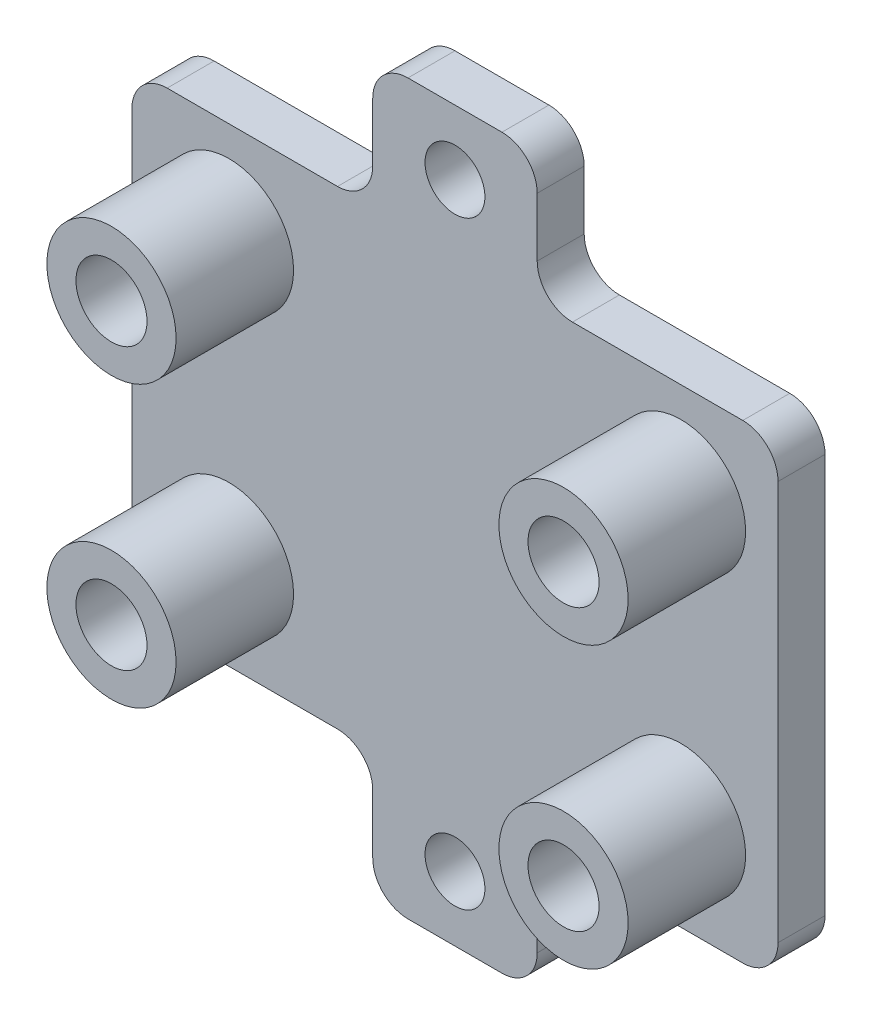
SolidWorks part; units mm, degrees
material "ABS"
ref_plane "X-Y Datum" through (0, 0, 0) normal (0, 0, 1) x (1, 0, 0)
ref_plane "X-Z Datum" through (0, 0, 0) normal (0, 1, 0) x (1, 0, 0)
ref_plane "Y-Z Datum" through (0, 0, 0) normal (1, 0, 0) x (0, 0, -1)
sketch "Sketch1" plane through (0, 0, 0) normal (0, 0, 1) x (1, 0, 0)
  line L1 (-22.987, 15.621) -> (22.987, 15.621) construction
  line L2 (-22.987, 15.621) -> (-22.987, -15.621) construction
  line L3 (-22.987, -15.621) -> (22.987, -15.621) construction
  line L4 (22.987, 15.621) -> (22.987, -15.621) construction
  line L5 (-22.987, 15.621) -> (22.987, -15.621) construction
  line L6 (-22.987, -15.621) -> (22.987, 15.621) construction
  line L7 (27.5, -20) -> (-27.5, -20)
  line L8 (27.5, -20) -> (27.5, 20)
  line L9 (27.5, 20) -> (-27.5, 20)
  line L10 (-27.5, -20) -> (-27.5, 20)
  line L11 (27.5, -20) -> (-27.5, 20) construction
  line L12 (27.5, 20) -> (-27.5, -20) construction
  point P0 (0, 0)
  point P6 (0, 0)
  dimension "D1" = 45.974
  dimension "D2" = 31.242
  dimension "D3" = 55
  dimension "D4" = 40
extrude "Boss-Extrude1" add sketch "Sketch1" along normal blind 4
sketch "Sketch3" plane through (0, 0, 4) normal (0, 0, 1) x (1, 0, 0)
  circle A4 centre (19.2405, -11.938) radius 2.1 construction
  circle A5 centre (-19.2405, -11.938) radius 2.1 construction
  circle A6 centre (19.2405, 11.938) radius 2.1 construction
  circle A7 centre (-19.2405, 11.938) radius 2.1 construction
  circle A8 centre (-19.2405, -11.938) radius 3.025
  circle A9 centre (-19.2405, 11.938) radius 3.025
  circle A10 centre (19.2405, 11.938) radius 3.025
  circle A11 centre (19.2405, -11.938) radius 3.025
  circle A12 centre (-19.2405, 11.938) radius 5.5
  circle A13 centre (-19.2405, -11.938) radius 5.5
  circle A14 centre (19.2405, 11.938) radius 5.5
  circle A15 centre (19.2405, -11.938) radius 5.5
  dimension "D1" = 4.2
  dimension "D2" = 6.05
  dimension "D3" = 11
extrude "Boss-Extrude2" add sketch "Sketch3" along normal blind 10
sketch "Sketch4" plane through (0, 0, 4) normal (0, 0, 1) x (1, 0, 0)
  line L0 (27.5, 20) -> (-27.5, 20) construction
  line L1 (-7, 31) -> (7, 31)
  line L2 (-7, 31) -> (-7, 20)
  line L3 (-7, 20) -> (7, 20)
  line L4 (7, 31) -> (7, 20)
  line L5 (-7, 31) -> (7, 20) construction
  line L6 (-7, 20) -> (7, 31) construction
  line L7 (0, 31) -> (0, 20) construction
  circle A0 centre (0, 25.5) radius 2.55
  point P0 (0, 25.5)
  point P9 (0, 25.5)
  dimension "D3" = 5.1
  dimension "D1" = 14
  dimension "D2" = 11
extrude "Boss-Extrude3" add sketch "Sketch4" against normal blind 4
mirror "Mirror2" about plane through (0, 0, 0) normal (0, 1, 0) of "Boss-Extrude3"
fillet "Fillet2" radius 3 12 edges at (-27.5, 20, 2) (27.5, 20, 2) (-27.5, -20, 2) (27.5, -20, 2) (7, 31, 2) (-7, 31, 2) (-7, 20, 2) (7, 20, 2) (7, -31, 2) (-7, -31, 2) (-7, -20, 2) (7, -20, 2)
